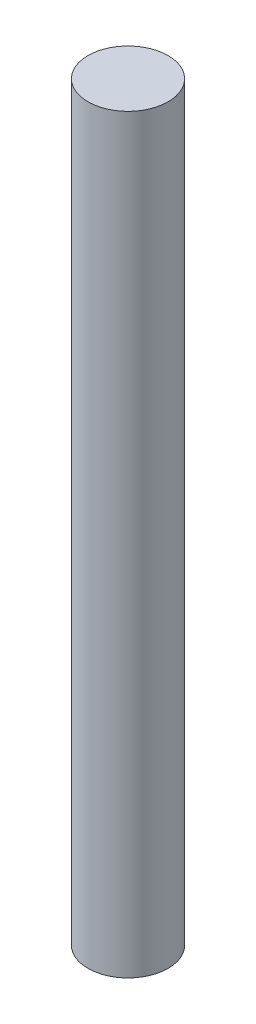
SolidWorks part; units mm, degrees
ref_plane "前视基准面" through (0, 0, 0) normal (0, 0, 1) x (1, 0, 0)
ref_plane "上视基准面" through (0, 0, 0) normal (0, 1, 0) x (1, 0, 0)
ref_plane "右视基准面" through (0, 0, 0) normal (1, 0, 0) x (0, 0, -1)
sketch "草图1" plane through (0, 0, 0) normal (0, 1, 0) x (1, 0, 0)
  circle A0 centre (0, 0) radius 1
  dimension "D1" = 2
extrude "凸台-拉伸1" add sketch "草图1" along normal blind 18.74
